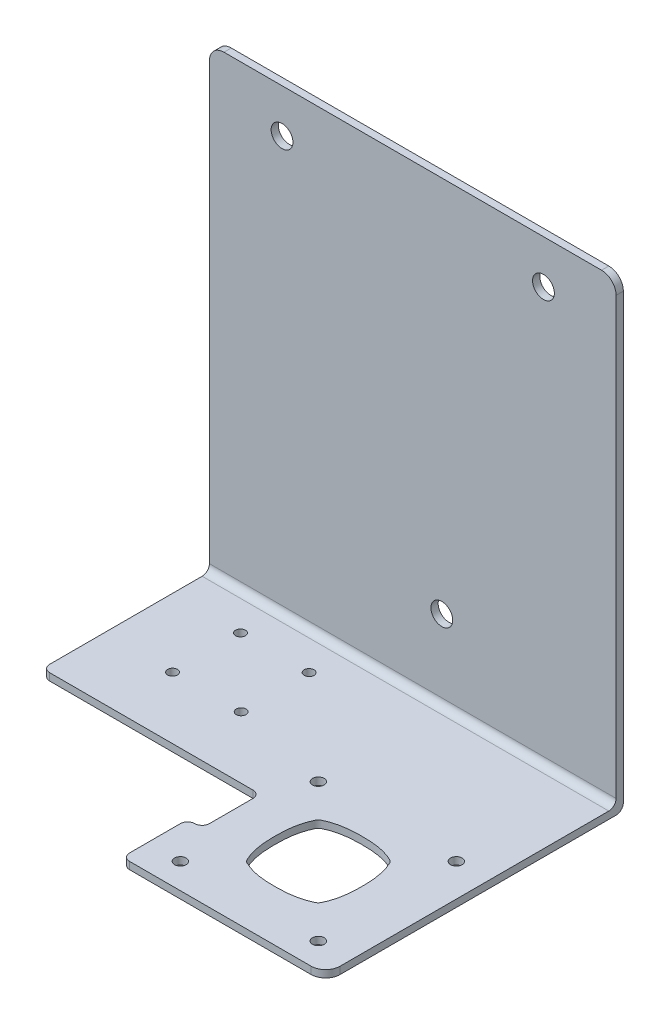
SolidWorks part; units mm, degrees
ref_plane "Front Plane" through (0, 0, 0) normal (0, 0, 1) x (1, 0, 0)
ref_plane "Top Plane" through (0, 0, 0) normal (0, 1, 0) x (1, 0, 0)
ref_plane "Right Plane" through (0, 0, 0) normal (1, 0, 0) x (0, 0, -1)
sketch "Sketch2" plane through (0, 0, 0) normal (0, 0, 1) x (1, 0, 0)
  line L1 (-88.9, -101.6) -> (88.9, -101.6)
  line L2 (-88.9, -101.6) -> (-88.9, 101.6)
  line L3 (-88.9, 101.6) -> (88.9, 101.6)
  line L4 (88.9, -101.6) -> (88.9, 101.6)
  line L5 (-88.9, -101.6) -> (88.9, 101.6) construction
  line L6 (-88.9, 101.6) -> (88.9, -101.6) construction
  point P0 (0, 0)
  dimension "D1" = 177.8
  dimension "D2" = 203.2
extrude "Boss-Extrude1" add sketch "Sketch2" along normal blind 3.175
sketch "Sketch3" plane through (0, 0, 3.175) normal (0, 0, 1) x (1, 0, 0)
  line L0 (88.9, -101.6) -> (88.9, 101.6) construction
  line L1 (-88.9, -101.6) -> (88.9, -101.6)
  line L2 (-88.9, -101.6) -> (-88.9, -98.425)
  line L3 (-88.9, -98.425) -> (88.9, -98.425)
  line L4 (88.9, -101.6) -> (88.9, -98.425)
  dimension "D1" = 3.175
extrude "Boss-Extrude2" add sketch "Sketch3" along normal blind 127
fillet "Fillet1" radius 3.175 2 edges at (0, -101.6, 0) (0, -98.425, 3.175)
fillet "Fillet2" radius 6.35 4 edges at (88.9, -100.0125, 130.175) (-88.9, -100.0125, 130.175) (88.9, 101.6, 1.5875) (-88.9, 101.6, 1.5875)
sketch "Sketch5" plane through (0, -98.425, 0) normal (0, 1, 0) x (1, 0, 0)
  line L0 (-88.9, -76.2) -> (6.35, -76.2)
  line L1 (-88.9, -123.825) -> (-88.9, -6.35) construction
  line L2 (6.35, -76.2) -> (6.35, -101.6)
  line L3 (6.35, -101.6) -> (0, -101.6)
  line L4 (0, -101.6) -> (0, -130.175)
  line L9 (82.55, -130.175) -> (-82.55, -130.175) construction
  dimension "D1" = 28.575
  dimension "D2" = 95.25
  dimension "D3" = 88.9
  dimension "D4" = 53.975
extrude "Cut-Extrude1" cut sketch "Sketch5" against normal through all and the other way through all flip side to cut
fillet "Fillet4" radius 3.175 5 edges at (6.35, -100.0125, 101.6) (-88.9, -100.0125, 76.2) (0, -100.0125, 130.175) (0, -100.0125, 101.6) (6.35, -100.0125, 76.2)
sketch "Sketch6" plane through (0, -98.425, 0) normal (0, 1, 0) x (1, 0, 0)
  line L0 (82.55, -130.175) -> (3.175, -130.175) construction
  line L1 (88.9, -123.825) -> (88.9, -6.35) construction
  circle A0 centre (74.6125, -119.0625) radius 2.54
  circle A1 centre (14.2875, -119.0625) radius 2.54
  circle A2 centre (14.2875, -58.7375) radius 2.54
  circle A3 centre (74.6125, -58.7375) radius 2.54
  circle A4 centre (-29.05, -49.14) radius 2.15
  circle A5 centre (-59.05, -49.14) radius 2.15
  circle A6 centre (-29.05, -19.44) radius 2.15
  circle A7 centre (-59.05, -19.44) radius 2.15
  dimension "D9" = 5.08
  dimension "D10" = 4.3
  dimension "D1" = 11.1125
  dimension "D2" = 71.4375
  dimension "D3" = 81.035
  dimension "D4" = 110.735
  dimension "D5" = 14.2875
  dimension "D6" = 74.6125
  dimension "D7" = 117.95
  dimension "D8" = 147.95
extrude "Cut-Extrude2" cut sketch "Sketch6" against normal through all
sketch "Sketch7" plane through (0, 0, 3.175) normal (0, 0, 1) x (1, 0, 0)
  line L0 (82.55, 101.6) -> (-82.55, 101.6) construction
  line L1 (-88.9, 95.25) -> (-88.9, -95.25) construction
  circle A0 centre (-57.15, 82.55) radius 4.7625
  circle A1 centre (57.15, 82.55) radius 4.7625
  circle A2 centre (12.7, -63.5) radius 4.7625
  dimension "D3" = 9.525
  dimension "D1" = 19.05
  dimension "D2" = 31.75
  dimension "D4" = 146.05
  dimension "D5" = 165.1
  dimension "D6" = 101.6
extrude "Cut-Extrude3" cut sketch "Sketch7" against normal through all
sketch "Sketch8" plane through (0, -98.425, 0) normal (0, 1, 0) x (1, 0, 0)
  spline S0 degree 3 poles (60.2354, -104.6854) (55.0057, -107.4198) (44.45, -108.4447) (33.8943, -107.4198) (28.6646, -104.6854) (25.9302, -99.4557) (24.9053, -88.9) (25.9302, -78.3443) (28.6646, -73.1146) (33.8943, -70.3802) (44.45, -69.3553) (55.0057, -70.3802) (60.2354, -73.1146) (62.9698, -78.3443) (63.9947, -88.9) (62.9698, -99.4557) (60.2354, -104.6854) (55.0057, -107.4198) (44.45, -108.4447) knots -0.133368 -0.016736 -0.008368 0 0.116632 0.233264 0.241632 0.25 0.366632 0.483264 0.491632 0.5 0.616632 0.733264 0.741632 0.75 0.866632 0.983264 0.991632 1 1.116632 1.233264 1.241632 only from (59.2485, -105.191) to (59.2485, -105.191)
extrude "Cut-Extrude4" cut sketch "Sketch8" against normal through all
